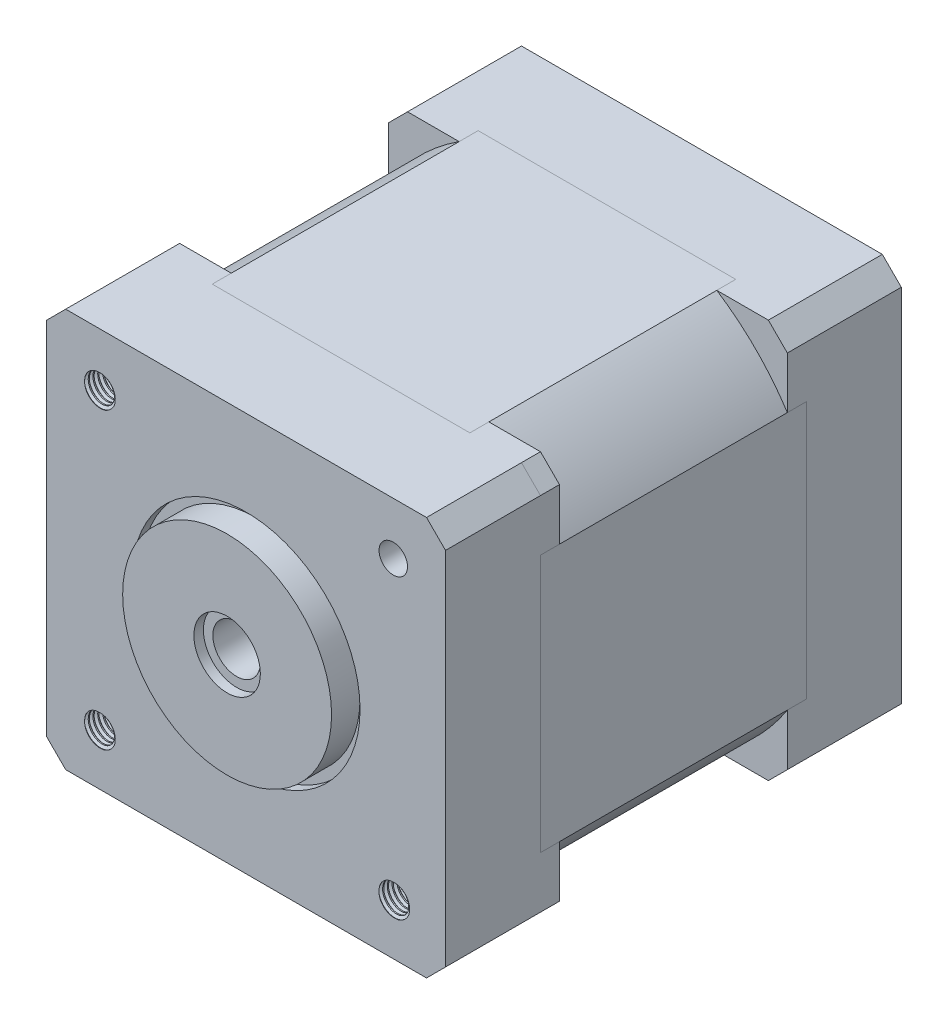
SolidWorks part; units mm, degrees
other "Cortar-Extruir6"
ref_plane "Alzado" through (0, 0, 0) normal (0, 0, 1) x (1, 0, 0)
ref_plane "Planta" through (0, 0, 0) normal (0, 1, 0) x (1, 0, 0)
ref_plane "Vista lateral" through (0, 0, 0) normal (1, 0, 0) x (0, 0, -1)
sketch "Croquis1" plane through (0, 0, 0) normal (0, 0, 1) x (1, 0, 0)
  line L1 (-21, -21) -> (21, -21)
  line L2 (-21, -21) -> (-21, 21)
  line L3 (-21, 21) -> (21, 21)
  line L4 (21, -21) -> (21, 21)
  line L5 (-21, -21) -> (21, 21) construction
  line L6 (-21, 21) -> (21, -21) construction
  point P0 (0, 0)
  dimension "D1" = 42
  dimension "D2" = 42
extrude "Saliente-Extruir2" add sketch "Croquis1" along normal blind 12
chamfer "Chaflán3" distance 2 angle 45 3 edges at (21, 21, 6) (21, -21, 6) (-21, -21, 6)
chamfer "Chaflán2" distance 2 angle 45 1 edges at (-21, 21, 6)
sketch "Croquis3" plane through (0, 0, 12) normal (0, 0, 1) x (1, 0, 0)
  line L0 (-13.5647, 21) -> (13.5647, 21)
  line L1 (19, 21) -> (-19, 21) construction
  line L2 (-21, 13.5647) -> (-21, -13.5647)
  line L3 (-21, 19) -> (-21, -19) construction
  line L4 (-13.5647, -21) -> (13.5647, -21)
  line L5 (-19, -21) -> (19, -21) construction
  line L6 (21, 13.5647) -> (21, -13.5647)
  line L7 (21, -19) -> (21, 19) construction
  arc A0 (-13.5647, 21) -> (-21, 13.5647) centre (0, 0) ccw
  arc A1 (-21, -13.5647) -> (-13.5647, -21) centre (0, 0) ccw
  arc A2 (13.5647, -21) -> (21, -13.5647) centre (0, 0) ccw
  arc A3 (21, 13.5647) -> (13.5647, 21) centre (0, 0) ccw
  dimension "D1" = 50
extrude "Cortar-Extruir1" cut sketch "Croquis3" against normal blind 2
sketch "Croquis11" plane through (0, 0, 10) normal (0, 0, 1) x (1, 0, 0)
  line L0 (-13.5647, 21) -> (13.5647, 21)
  line L1 (-13.5647, -21) -> (13.5647, -21)
  line L2 (21, 13.5647) -> (21, -13.5647)
  line L3 (-21, 13.5647) -> (-21, -13.5647)
  arc A0 (-13.5647, 21) -> (-21, 13.5647) centre (0, 0) ccw
  arc A1 (21, 13.5647) -> (13.5647, 21) centre (0, 0) ccw
  arc A2 (13.5647, -21) -> (21, -13.5647) centre (0, 0) ccw
  arc A3 (-21, -13.5647) -> (-13.5647, -21) centre (0, 0) ccw
  dimension "D1" = 50
  dimension "D2" = 21
  dimension "D3" = 21
  dimension "D4" = 21
  dimension "D5" = 21
extrude "Saliente-Extruir9" add sketch "Croquis11" along normal blind 28 separate body
ref_plane "Plano2" through (0, 0, 38) normal (0, 0, 1) x (1, 0, 0)
sketch "Croquis14" plane through (0, 0, 38) normal (0, 0, 1) x (1, 0, 0)
  line L1 (-21, -21) -> (21, -21)
  line L2 (-21, -21) -> (-21, 21)
  line L3 (-21, 21) -> (21, 21)
  line L4 (21, -21) -> (21, 21)
  line L5 (-21, -21) -> (21, 21) construction
  line L6 (-21, 21) -> (21, -21) construction
  point P0 (0, 0)
  dimension "D1" = 42
  dimension "D2" = 42
extrude "Saliente-Extruir11" add sketch "Croquis14" along normal blind 10 separate body
chamfer "Chaflán6" distance 2 angle 45 4 edges at (-21, 21, 43) (21, 21, 43) (21, -21, 43) (-21, -21, 43)
sketch "Croquis17" plane through (0, 0, 38) normal (0, 0, 1) x (1, 0, 0)
  line L0 (13.5647, 21) -> (21, 21)
  line L1 (-21, -21) -> (-13.5647, -21)
  line L2 (-21, -21) -> (-21, -13.5647)
  line L3 (-21, 21) -> (-13.5647, 21)
  line L4 (21, -21) -> (21, -13.5647)
  line L5 (-21, -21) -> (21, 21) construction
  line L6 (-21, 21) -> (21, -21) construction
  line L7 (-21, 13.5647) -> (-21, 21)
  line L8 (21, 13.5647) -> (21, 21)
  line L9 (13.5647, -21) -> (21, -21)
  arc A0 (-13.5647, 21) -> (-21, 13.5647) centre (0, 0) ccw
  arc A1 (21, 13.5647) -> (13.5647, 21) centre (0, 0) ccw
  arc A2 (-21, -13.5647) -> (-13.5647, -21) centre (0, 0) ccw
  arc A3 (13.5647, -21) -> (21, -13.5647) centre (0, 0) ccw
  dimension "D1" = 50
  dimension "D2" = 42
  dimension "D3" = 42
extrude "Saliente-Extruir12" add sketch "Croquis17" against normal blind 2
chamfer "Chaflán7" distance 2 angle 45 4 edges at (-21, -21, 37) (-21, 21, 37) (21, 21, 37) (21, -21, 37)
sketch "Croquis18" plane through (0, 0, 48) normal (0, 0, 1) x (1, 0, 0)
  circle A0 centre (0, 0) radius 12
  dimension "D1" = 24
extrude "Cortar-Extruir4" cut sketch "Croquis18" against normal blind 1
sketch "Croquis20" plane through (0, 0, 47) normal (0, 0, 1) x (1, 0, 0)
  circle A0 centre (0, 0) radius 11
  dimension "D1" = 22
extrude "Saliente-Extruir14" add sketch "Croquis20" along normal blind 3
sketch "Croquis21" plane through (0, 0, 50) normal (0, 0, 1) x (1, 0, 0)
  circle A0 centre (0, 0) radius 3.5
  dimension "D1" = 7
extrude "Cortar-Extruir5" cut sketch "Croquis21" against normal blind 1
sketch "Croquis22" plane through (0, 0, 49) normal (0, 0, 1) x (1, 0, 0)
  circle A0 centre (0, 0) radius 2.5
  dimension "D1" = 5
extrude "Cortar-Extruir6" cut sketch "Croquis22" against normal through all
chamfer "Chaflán8" distance 0.5 angle 45 1 edges at (2.5, 0, 0)
sketch "Croquis23" plane through (0, 0, 48) normal (0, 0, 1) x (1, 0, 0)
  line L0 (-33.0137, 0) -> (33.3501, 0) construction
  line L1 (0, 27.0021) -> (0, -27.9173) construction
  circle A0 centre (-15.5, 15.5) radius 1.5
  circle A1 centre (15.5, 15.5) radius 1.5
  circle A2 centre (15.5, -15.5) radius 1.5
  circle A3 centre (-15.5, -15.5) radius 1.5
  dimension "D1" = 3
  dimension "D2" = 31
  dimension "D3" = 31
  dimension "D4" = 31
  dimension "D5" = 31
extrude "Cortar-Extruir7" cut sketch "Croquis23" against normal blind 4.5
thread "Rosca1" pitch 0.5 method cut profile "Perfil de rosca2" start angle 0, offset 1, length 5, pitch 0.5, diameter 3
ref_plane "Plano4" through (-17, 15.5, 49) normal (0, -1, 0) x (-1, 0, 0)
sketch "Perfil de rosca2" plane through (-17, 15.5, 49) normal (0, -1, 0) x (-1, 0, 0)
  line L0 (0, 0) -> (0, 0.5) construction
  line L1 (0, 0) -> (0.2706, 0.1562)
  line L2 (0.2706, 0.1562) -> (0.2706, 0.2187)
  line L3 (0.2706, 0.2187) -> (0, 0.375)
  line L4 (0.2706, 0.1875) -> (0, 0.1875) construction
  line L11 (0, 0) -> (0, 0.375)
  point P2 (0, 0)
  dimension "Pitch" = 0.5
  dimension "Profile_Angle" = 60
  dimension "Profile_Land" = 0.0625
  dimension "Profile_Height" = 0.2706
thread "Rosca2" pitch 0.5 method cut profile "Perfil de rosca3" start angle 0, offset 1, length 5, pitch 0.5, diameter 3
ref_plane "Plano5" through (-17, -15.5, 49) normal (0, -1, 0) x (-1, 0, 0)
sketch "Perfil de rosca3" plane through (-17, -15.5, 49) normal (0, -1, 0) x (-1, 0, 0)
  line L0 (0, 0) -> (0, 0.5) construction
  line L1 (0, 0) -> (0.2706, 0.1562)
  line L2 (0.2706, 0.1562) -> (0.2706, 0.2187)
  line L3 (0.2706, 0.2187) -> (0, 0.375)
  line L4 (0.2706, 0.1875) -> (0, 0.1875) construction
  line L11 (0, 0) -> (0, 0.375)
  point P2 (0, 0)
  dimension "Pitch" = 0.5
  dimension "Profile_Angle" = 60
  dimension "Profile_Land" = 0.0625
  dimension "Profile_Height" = 0.2706
thread "Rosca3" pitch 0.5 method cut profile "Perfil de rosca4" start angle 0, offset 1, length 5, pitch 0.5, diameter 3
ref_plane "Plano6" through (14, -15.5, 49) normal (0, -1, 0) x (-1, 0, 0)
sketch "Perfil de rosca4" plane through (14, -15.5, 49) normal (0, -1, 0) x (-1, 0, 0)
  line L0 (0, 0) -> (0, 0.5) construction
  line L1 (0, 0) -> (0.2706, 0.1562)
  line L2 (0.2706, 0.1562) -> (0.2706, 0.2187)
  line L3 (0.2706, 0.2187) -> (0, 0.375)
  line L4 (0.2706, 0.1875) -> (0, 0.1875) construction
  line L11 (0, 0) -> (0, 0.375)
  point P2 (0, 0)
  dimension "Pitch" = 0.5
  dimension "Profile_Angle" = 60
  dimension "Profile_Land" = 0.0625
  dimension "Profile_Height" = 0.2706
